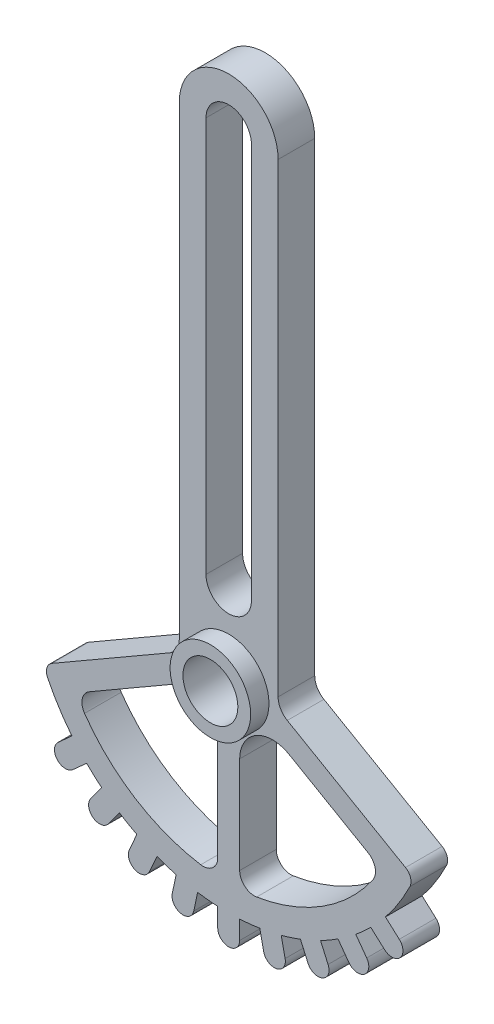
SolidWorks part; units mm, degrees
note: The reader was unsure of these and kept them because the rebuilt part matched: shared geometry of "Sketch5<2>".
ref_plane "Front Plane" through (0, 0, 0) normal (0, 0, 1) x (1, 0, 0)
ref_plane "Top Plane" through (0, 0, 0) normal (0, 1, 0) x (1, 0, 0)
ref_plane "Right Plane" through (0, 0, 0) normal (1, 0, 0) x (0, 0, -1)
sketch "Sketch1" plane through (0, 0, 0) normal (0, 0, 1) x (1, 0, 0)
  line L0 (-13.5, 0) -> (-13.5, 130)
  line L1 (13.5, 130) -> (13.5, 0)
  line L2 (13.5, 0) -> (-13.5, 0)
  line L3 (-13.5, 0) -> (-13.5, -0.1132)
  line L4 (0, 130) -> (0, 22) construction
  line L5 (6.2, 130) -> (6.2, 22)
  line L6 (-6.2, 130) -> (-6.2, 22)
  line L7 (-13.5, 0) -> (-50.6463, -21.4464)
  line L8 (13.5, 0) -> (13.5, -0.1132)
  line L9 (13.5, 0) -> (50.6463, -21.4464)
  line L10 (0, 22) -> (0, -78.0689) construction
  arc A0 (-13.5, 130) -> (13.5, 130) centre (0, 130) cw
  arc A1 (6.2, 130) -> (-6.2, 130) centre (0, 130) ccw
  arc A2 (-6.2, 22) -> (6.2, 22) centre (0, 22) ccw
  arc A6 (-50.6463, -21.4464) -> (50.6463, -21.4464) centre (0, 0) ccw
  point P10 (0, 76)
  point P17 (0, -55)
  point P21 (13.5, 0)
  point P24 (-13.5, 0)
  dimension "D3" = 13.5
  dimension "D6" = 6.2
  dimension "D9" = 60
  dimension "D13" = 110
  dimension "D1" = 130
  dimension "D2" = 27
  dimension "D4" = 22
  dimension "D5" = 108
  dimension "D10" = 60
  dimension "D14" = 55
  dimension "D15" = 50.6463
  dimension "D16" = 50.6463
extrude "Boss-Extrude1" add sketch "Sketch1" along normal mid plane 10
sketch "Sketch4" plane through (0, 0, 0) normal (0, 0, 1) x (1, 0, 0)
  line L0 (0, 0) -> (0, -66.424) construction
  line L1 (-3, -54.9181) -> (-3, -60)
  line L2 (3, -60) -> (3, -54.9181)
  line L7 (-13.5, 130) -> (-13.5, 0)
  line L8 (-13.5, 0) -> (-50.6463, -21.4464)
  line L9 (50.6463, -21.4464) -> (13.5, 0)
  line L10 (-13.5, 130) -> (-13.5, 0)
  line L11 (13.5, 0) -> (13.5, 130)
  line L12 (13.5, 0) -> (13.5, 130)
  arc A1 (-3, -60) -> (3, -60) centre (0, -60) ccw
  arc A2 (-50.6463, -21.4464) -> (50.6463, -21.4464) centre (0, 0) ccw construction
  arc A6 (13.5, 130) -> (-13.5, 130) centre (0, 130) ccw
  arc A8 (-50.6463, -21.4464) -> (50.6463, -21.4464) centre (0, 0) ccw
  arc A12 (-3, -54.9181) -> (3, -54.9181) centre (0, 0) ccw
  dimension "D1" = 3
  dimension "D2" = 60
  dimension "D3" = 0
sketch "Sketch5" plane through (0, 0, 0) normal (0, 0, 1) x (1, 0, 0)
  circle A0 centre (0, 0) radius 7.5
  circle A1 centre (0, 0) radius 11
  dimension "D1" = 22
  dimension "D2" = 15
extrude "Boss-Extrude3" add sketch "Sketch5" along normal blind 10
extrude "Cut-Extrude2" cut sketch "Sketch5<2>" against normal through all both and the other way through all contours A0
sketch "Sketch5<2>" plane through (0, 0, 0) normal (0, 0, 1) x (1, 0, 0) same geometry as "Sketch5"
fillet "Fillet1" radius 3 1 edges at (7.5, 0, -5)
fillet "Fillet2" radius 3 2 edges at (-50.6463, -21.4464, 0) (50.6463, -21.4464, 0)
fillet "Fillet3" radius 5 2 edges at (13.5, 0, 0) (-13.5, 0, 0)
extrude "Boss-Extrude4" add sketch "Sketch4" along normal mid plane 10 contours L1 A1 L2 A12
pattern_circular "CirPattern1" count 5 every 12 about axis through (0, 0, 0) along (0, 0, 1) of "Boss-Extrude4"
sketch "Sketch6" plane through (0, 0, 0) normal (0, 0, 1) x (1, 0, 0)
  line L0 (0, 0) -> (0, -75.6896) construction
  line L1 (-3, -17.0318) -> (-3, -43.4396)
  line L2 (-38.0915, -21.7034) -> (-16.5, -9.2376)
  line L3 (-16, -1.4434) -> (-48.2911, -20.0866) construction
  arc A0 (-7.6364, -47.3887) -> (-39.3725, -27.4555) centre (0, 0) cw
  arc A1 (-3, -43.4396) -> (-7.6364, -47.3887) centre (-7, -43.4396) cw
  arc A2 (-38.0915, -21.7034) -> (-39.3725, -27.4555) centre (-36.0915, -25.1675) ccw
  arc A3 (-3, -17.0318) -> (-16.5, -9.2376) centre (-12, -17.0318) ccw
  point P15 (-3, -47.9062)
  point P18 (-41.6937, -23.7832)
  dimension "D1" = 48
  dimension "D4" = 4
  dimension "D5" = 9
  dimension "D2" = 3
  dimension "D3" = 6.5
extrude "Cut-Extrude3" cut sketch "Sketch6" against normal through all both and the other way through all
mirror "Mirror1" about plane through (0, 0, 0) normal (1, 0, 0) of "Cut-Extrude3"
